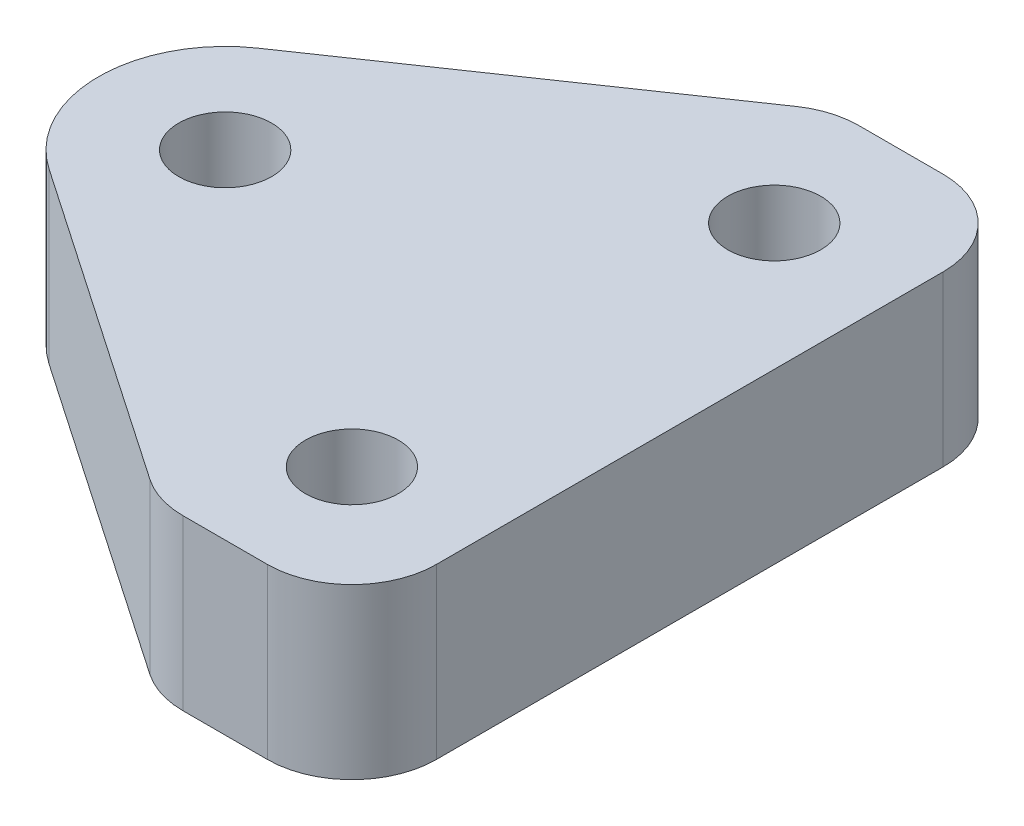
SolidWorks part; units mm, degrees
material "ABS"
ref_plane "Front Plane" through (0, 0, 0) normal (0, 0, 1) x (1, 0, 0)
ref_plane "Top Plane" through (0, 0, 0) normal (0, 1, 0) x (1, 0, 0)
ref_plane "Right Plane" through (0, 0, 0) normal (1, 0, 0) x (0, 0, -1)
ref_axis "X" through (-88.99, 0, 0) along (1, 0, 0)
ref_axis "Y" through (0, 55, 0) along (0, -1, 0)
ref_axis "Z" through (0, 0, -88.99) along (0, 0, 1)
sketch "Sketch1" plane through (0, 0, 0) normal (0, 1, 0) x (1, 0, 0)
  line L0 (0, 0) -> (20, 0) construction
  line L1 (20, 0) -> (20, 12.5) construction
  line L2 (20, 0) -> (20, -12.5) construction
  line L3 (-4.2345, -6.1902) -> (14.677, -19.1268)
  line L4 (17.5, -20) -> (22.5, -20)
  line L5 (27.5, -15) -> (27.5, 15)
  line L6 (22.5, 20) -> (17.5, 20)
  line L7 (14.677, 19.1268) -> (-4.2345, 6.1902)
  line L8 (20, 0) -> (27.5, 0) construction
  line L9 (20, 12.5) -> (20, 20) construction
  line L10 (20, -12.5) -> (20, -20) construction
  circle A0 centre (0, 0) radius 2.5 construction
  circle A1 centre (20, 12.5) radius 2.5 construction
  circle A2 centre (20, -12.5) radius 2.5 construction
  arc A3 (-4.2345, 6.1902) -> (-4.2345, -6.1902) centre (0, 0) ccw
  arc A4 (14.677, -19.1268) -> (17.5, -20) centre (17.5, -15) ccw
  arc A5 (22.5, -20) -> (27.5, -15) centre (22.5, -15) ccw
  arc A6 (27.5, 15) -> (22.5, 20) centre (22.5, 15) ccw
  arc A7 (17.5, 20) -> (14.677, 19.1268) centre (17.5, 15) ccw
  point P22 (20, 18.2305)
  point P25 (-4.8983, -6.7646)
  dimension "D1" = 20
  dimension "D2" = 5
  dimension "D3" = 25
  dimension "D4" = 5
  dimension "D7" = 5
  dimension "D5" = 7.5
  dimension "D6" = 40
extrude "Boss-Extrude1" add sketch "Sketch1" along normal blind 10
sketch "Sketch4" plane through (0, 10, 0) normal (0, 1, 0) x (1, 0, 0)
  point P0 (0, 0)
  point P3 (20, 12.5)
  point P6 (20, -12.5)
hole_wizard "M5 Clearance Hole1" positions "Sketch4" profile "Sketch3" hole size "M5" standard "ANSI Metric" end condition through all
sketch "Sketch3" plane through (0, 10, 0) normal (1, 0, 0) x (0, 0, 1)
  line L0 (0, 0) -> (0, 10)
  line L1 (0, 10) -> (2.75, 10)
  line L2 (2.75, 10) -> (2.75, 0)
  line L5 (2.75, 0) -> (0, 0)
  line L11 (0, -6.35) -> (0, 107.95) construction
  dimension "Thru Hole Dia." = 5.5
  dimension "Thru Hole Depth" = 10
